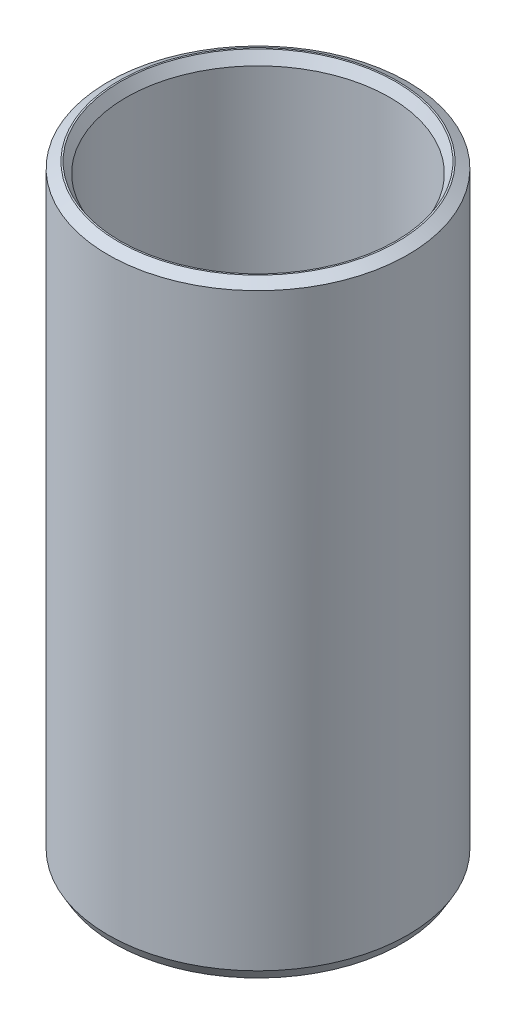
SolidWorks part; units mm, degrees
ref_plane "Front Plane" through (0, 0, 0) normal (0, 0, 1) x (1, 0, 0)
ref_plane "Top Plane" through (0, 0, 0) normal (0, 1, 0) x (1, 0, 0)
ref_plane "Right Plane" through (0, 0, 0) normal (1, 0, 0) x (0, 0, -1)
sketch "Sketch1" plane through (0, 0, 0) normal (0, 1, 0) x (1, 0, 0)
  circle A0 centre (0, 0) radius 55
  dimension "SLEEVE_OD" = 110
extrude "Boss-Extrude1" add sketch "Sketch1" along normal blind 222.2558
sketch "Sketch2" plane through (0, 0, 0) normal (0, 1, 0) x (1, 0, 0)
  circle A0 centre (0, 0) radius 48.3796
  dimension "BORE_D" = 96.7593
extrude "Cut-Extrude1" cut sketch "Sketch2" along normal through all
chamfer "Chamfer1" distance 2.2198 angle 60 4 edges at (0, 222.2558, 48.3796) (0, 0, 48.3796) (0, 0, 55) (0, 222.2558, 55) first distance on face at (0, 222.2558, 48.3796) first distance on face at (0, 0, 48.3796) first distance on face at (0, 222.2558, 55)
